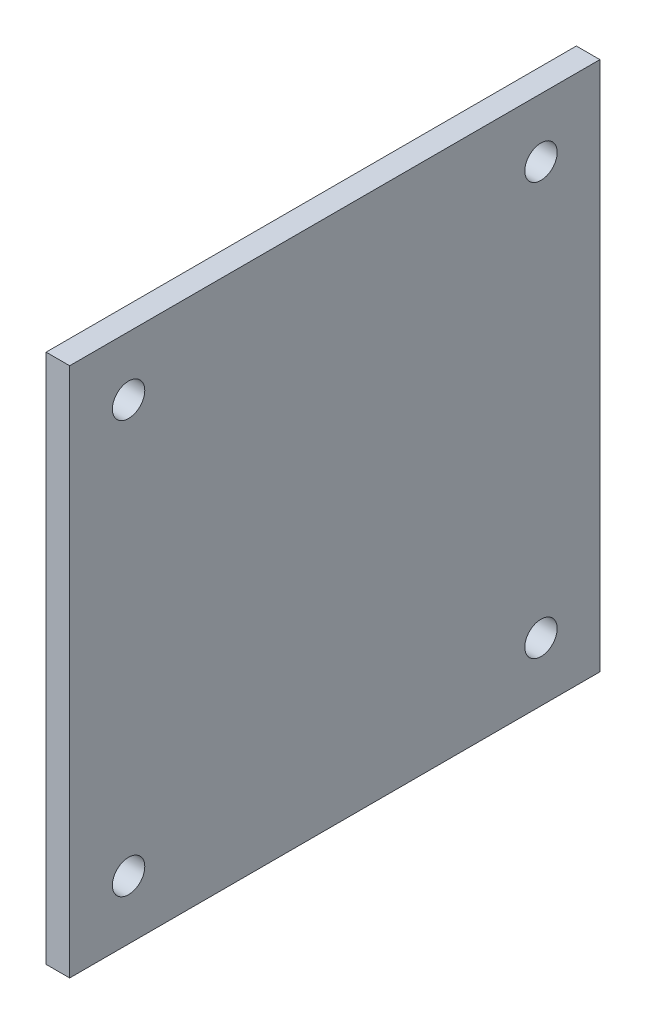
SolidWorks part; units mm, degrees
ref_plane "Front Plane" through (0, 0, 0) normal (0, 0, 1) x (1, 0, 0)
ref_plane "Top Plane" through (0, 0, 0) normal (0, 1, 0) x (1, 0, 0)
ref_plane "Right Plane" through (0, 0, 0) normal (1, 0, 0) x (0, 0, -1)
sketch "Plate Sketch" plane through (0, 0, 0) normal (1, 0, 0) x (0, 0, -1)
  line L0 (18, -18) -> (18, 18)
  line L1 (18, 18) -> (-18, 18)
  line L2 (-18, 18) -> (-18, -18)
  line L3 (-18, -18) -> (18, -18)
  circle A0 centre (14, -14) radius 1.1
  circle A1 centre (-14, -14) radius 1.1
  circle A2 centre (14, 14) radius 1.1
  circle A3 centre (-14, 14) radius 1.1
extrude "Plate" add sketch "Plate Sketch" against normal blind 1.6 from offset 37.6 offset against normal yes
ref_axis "Engine Axis" through (-37.29, 0, 0) along (-1, 0, 0)
sketch "BNO085 Sketch" plane through (0, 0, 0) normal (1, 0, 0) x (0, 0, -1)
  line L0 (11.35, -12.8) -> (11.35, 12.8)
  line L1 (11.35, 12.8) -> (-11.35, 12.8)
  line L2 (-11.35, 12.8) -> (-11.35, -12.8)
  line L3 (-11.35, -12.8) -> (11.35, -12.8)
extrude "BNO085" add sketch "BNO085 Sketch" against normal blind 4.6 from offset 39.2 offset against normal yes
